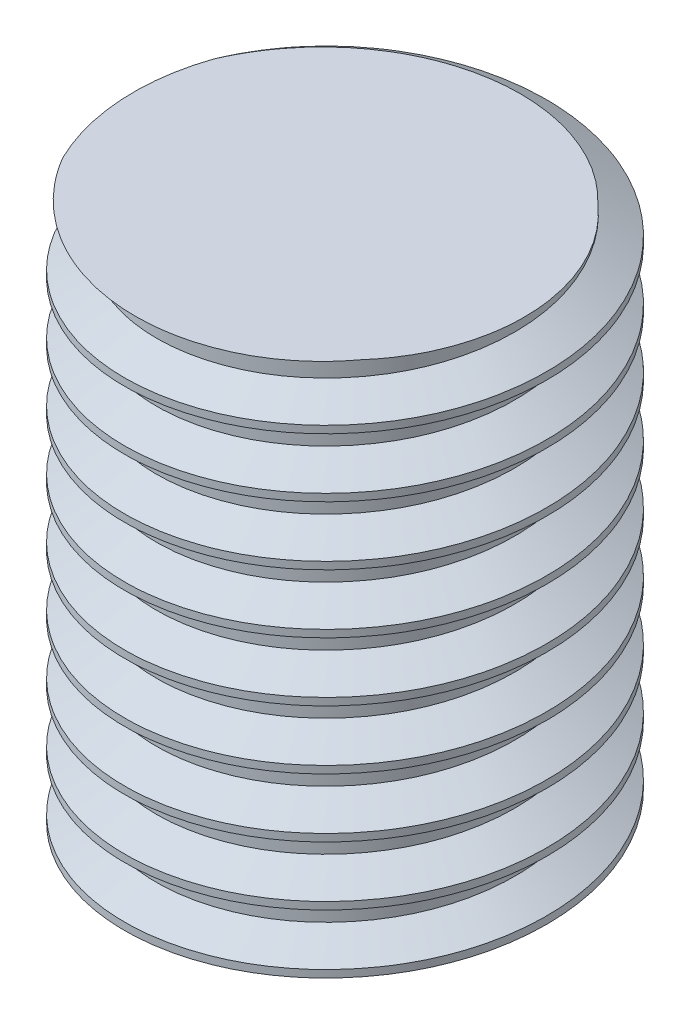
SolidWorks part; units mm, degrees
material "6061-T6 (SS)"
ref_plane "Front Plane" through (0, 0, 0) normal (0, 0, 1) x (1, 0, 0)
ref_plane "Top Plane" through (0, 0, 0) normal (0, 1, 0) x (1, 0, 0)
ref_plane "Right Plane" through (0, 0, 0) normal (1, 0, 0) x (0, 0, -1)
sketch "Sketch1" plane through (0, 0, 0) normal (0, 1, 0) x (1, 0, 0)
  circle A1 centre (0, 0) radius 7.5819
  dimension "D2" = 15.1638
extrude "Boss-Extrude2" add sketch "Sketch1" along normal blind 19.05
sketch "Sketch2" plane through (0, 0, 0) normal (0, -1, 0) x (1, 0, 0)
  circle A0 centre (0, 0) radius 5.9944
  dimension "D1" = 11.9888
extrude "Cut-Extrude1" cut sketch "Sketch2" against normal blind 12.7
thread "Thread1" pitch 2.1167 start angle 0, offset 21.32, length 25.4, pitch 2.1167, diameter 15.1638
ref_plane "Plane1" through (-7.5819, -2.27, 0) normal (0, 0, 1) x (-1, 0, 0)
sketch "Thread Profile1" plane through (-7.5819, -2.27, 0) normal (0, 0, 1) x (-1, 0, 0)
  line L0 (0, 0) -> (0, 2.1167) construction
  line L11 (0, 0) -> (0, 1.8521)
  line L12 (0, 1.8521) -> (-1.1457, 1.1906)
  line L13 (-1.1457, 1.1906) -> (-1.1457, 0.6615)
  line L15 (-1.1457, 0.6615) -> (0, 0)
  line L17 (-1.1457, 0.926) -> (0, 0.926) construction
  point P2 (0, 0)
  dimension "Pitch" = 2.1167
  dimension "Profile_Angle" = 60
  dimension "Profile_Land" = 0.5292
  dimension "Profile_Height" = 1.1457
